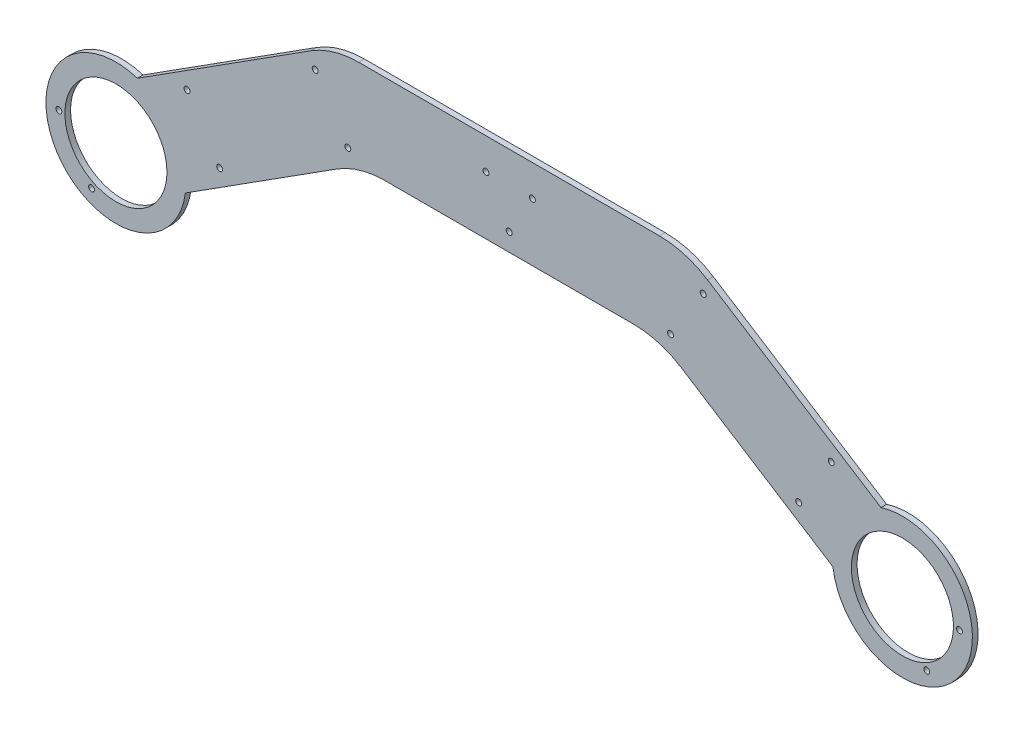
SolidWorks part; units mm, degrees
ref_plane "Front Plane" through (0, 0, 0) normal (0, 0, 1) x (1, 0, 0)
ref_plane "Top Plane" through (0, 0, 0) normal (0, 1, 0) x (1, 0, 0)
ref_plane "Right Plane" through (0, 0, 0) normal (1, 0, 0) x (0, 0, -1)
sketch "Sketch1" plane through (0, 0, 0) normal (0, 0, 1) x (1, 0, 0)
  line L0 (0, -33.2132) -> (0, -83.2132) construction
  line L1 (84.0896, -33.2132) -> (-84.0896, -33.2132)
  line L2 (-110.9546, -41.0436) -> (-262.9512, -137.8762)
  line L3 (-262.9512, -137.8762) -> (-236.0862, -180.0457)
  line L4 (-236.0862, -180.0457) -> (-96.3809, -91.0436)
  line L5 (-69.5159, -83.2132) -> (69.5159, -83.2132)
  line L6 (96.3809, -91.0436) -> (236.0862, -180.0457)
  line L7 (236.0862, -180.0457) -> (262.9512, -137.8762)
  line L8 (262.9512, -137.8762) -> (110.9546, -41.0436)
  line L9 (-98.6633, -33.2132) -> (0, 29.6422) construction
  line L10 (0, 29.6422) -> (98.6633, -33.2132) construction
  line L11 (-249.5187, -158.9609) -> (-220, -140.1555) construction
  line L12 (249.5187, -158.9609) -> (220, -140.1555) construction
  line L13 (-330, -140.1555) -> (-110, -140.1555) construction
  line L14 (-110, -140.1555) -> (110, -140.1555) construction
  line L15 (0, 0) -> (17.6777, -17.6777) construction
  line L16 (28.2843, -7.0711) -> (7.0711, -28.2843) construction
  line L17 (-7.0711, -28.2843) -> (-17.6777, -17.6777) construction
  line L18 (-17.6777, -17.6777) -> (17.6777, 17.6777) construction
  line L19 (17.6777, 17.6777) -> (28.2843, 7.0711) construction
  line L20 (17.6777, 17.6777) -> (67.5526, 17.6777) construction
  line L21 (0, -35.3553) -> (35.3553, 0) construction
  line L22 (0, 0) -> (5.7126, -24.3386) construction
  line L23 (-8.8906, -27.7661) -> (20.3157, -20.911) construction
  circle A1 centre (0, 0) radius 7.9375 construction
  circle A2 centre (-220, -140.1555) radius 110 construction
  circle A3 centre (220, -140.1555) radius 110 construction
  arc A4 (28.2843, -7.0711) -> (28.2843, 7.0711) centre (21.2132, 0) ccw construction
  arc A5 (7.0711, -28.2843) -> (-7.0711, -28.2843) centre (0, -21.2132) cw construction
  arc A6 (69.5159, -83.2132) -> (96.3809, -91.0436) centre (69.5159, -133.2132) cw
  arc A7 (-96.3809, -91.0436) -> (-69.5159, -83.2132) centre (-69.5159, -133.2132) cw
  arc A8 (110.9546, -41.0436) -> (84.0896, -33.2132) centre (84.0896, -83.2132) ccw
  arc A9 (-84.0896, -33.2132) -> (-110.9546, -41.0436) centre (-84.0896, -83.2132) ccw
  circle A10 centre (0, 0) radius 7.9375 construction
  arc A11 (20.3157, -20.911) -> (27.7661, -8.8906) centre (18.0307, -11.1756) ccw construction
  point P26 (17.6777, -17.6777)
  point P33 (35.3553, 0)
  point P36 (0, -35.3553)
  point P40 (0, -31.2132)
  dimension "D12" = 50
  dimension "D2" = 220
  dimension "D1" = 50
  dimension "D3" = 115
  dimension "D5" = 35
  dimension "D8" = 45
  dimension "D10" = 2
extrude "Base" add sketch "Sketch1" along normal blind 3.175
fillet "Fillet1" radius 10 4 edges at (262.9512, -137.8762, 1.5875) (236.0862, -180.0457, 1.5875) (-236.0862, -180.0457, 1.5875) (-262.9512, -137.8762, 1.5875)
sketch "Sketch2" plane through (0, 0, 3.175) normal (0, 0, 1) x (1, 0, 0)
  line L0 (0, -33.2132) -> (0, -83.2132) construction
  line L1 (84.0896, -33.2132) -> (-84.0896, -33.2132) construction
  line L2 (-69.5159, -83.2132) -> (69.5159, -83.2132) construction
  circle A0 centre (0, -58.2132) radius 15 construction
  circle A1 centre (-12.9904, -50.7132) radius 1.65
  circle A2 centre (12.9904, -50.7132) radius 1.65
  circle A3 centre (0, -73.2132) radius 1.65
  point P17 (0, -58.2132)
  dimension "D1" = 30
  dimension "D2" = 3.3
  dimension "D3" = 3
extrude "Adapter Attachment" cut sketch "Sketch2" against normal through all
sketch "Sketch3" plane through (0, 0, 3.175) normal (0, 0, 1) x (1, 0, 0)
  line L0 (-258.9072, -138.7727) -> (-249.1443, -140.9371) construction
  line L1 (-235.1897, -176.0018) -> (-233.0253, -166.2388) construction
  line L2 (-251.9057, -140.3249) -> (-256.2041, -133.5778) construction
  line L3 (-233.6375, -169.0002) -> (-229.3391, -175.7473) construction
  line L4 (-110.9546, -41.0436) -> (-254.5173, -132.5032) construction
  line L5 (-227.6523, -174.6727) -> (-96.3809, -91.0436) construction
  line L6 (0, -1.7463) -> (0, 1.7463) construction
  arc A0 (-254.5173, -132.5032) -> (-257.5782, -146.3101) centre (-249.1443, -140.9371) ccw construction
  arc A1 (-241.4592, -171.6118) -> (-227.6523, -174.6727) centre (-233.0253, -166.2388) ccw construction
  circle A2 centre (-251.9057, -140.3249) radius 1.65
  circle A3 centre (-233.6375, -169.0002) radius 1.65
  circle A4 centre (-161.9492, -123.3297) radius 1.65
  circle A5 centre (-180.2174, -94.6544) radius 1.65
  circle A6 centre (-90.2609, -77.6593) radius 1.65
  circle A7 centre (-108.5291, -48.984) radius 1.65
  circle A8 centre (108.5291, -48.984) radius 1.65
  circle A9 centre (90.2609, -77.6593) radius 1.65
  circle A10 centre (180.2174, -94.6544) radius 1.65
  circle A11 centre (161.9492, -123.3297) radius 1.65
  circle A12 centre (251.9057, -140.3249) radius 1.65
  circle A13 centre (233.6375, -169.0002) radius 1.65
  dimension "D2" = 3.3
  dimension "D1" = 8
  dimension "D4" = 85
  dimension "D3" = 3
extrude "Strut Holes" cut sketch "Sketch3" against normal through all
sketch "Sketch4" plane through (0, 0, 3.175) normal (0, 0, 1) x (1, 0, 0)
  line L0 (-241.9667, -135.2856) -> (-215.1301, -118.1888) construction
  line L1 (-110.9546, -41.0436) -> (-262.9512, -137.8762) construction
  line L2 (0, -1.7463) -> (0, 1.7463) construction
  circle A0 centre (-220, -140.1555) radius 16.05
  circle A1 centre (-220, -140.1555) radius 22.5 construction
  circle A2 centre (-241.9667, -135.2856) radius 2.75
  circle A3 centre (-215.1301, -118.1888) radius 2.75
  circle A4 centre (-198.0333, -145.0253) radius 2.75
  circle A5 centre (-224.8699, -162.1221) radius 2.75
  circle A6 centre (224.8699, -162.1221) radius 2.75
  circle A7 centre (241.9667, -135.2856) radius 2.75
  circle A8 centre (198.0333, -145.0253) radius 2.75
  circle A9 centre (215.1301, -118.1888) radius 2.75
  circle A10 centre (220, -140.1555) radius 16.05
  point P15 (-220, -140.1555)
  dimension "D1" = 32.1
  dimension "D2" = 45
  dimension "D4" = 5.5
  dimension "D3" = 4
extrude "Motor Connection" [suppressed] cut sketch "Sketch4" against normal through all
sketch "Sketch5" plane through (0, 0, 3.175) normal (0, 0, 1) x (1, 0, 0)
  line L0 (0, -1.7463) -> (0, 1.7463) construction
  circle A0 centre (-220, -140.1555) radius 28.55
  circle A1 centre (-220, -140.1555) radius 39.1548
  arc A2 (-254.5173, -132.5032) -> (-257.5782, -146.3101) centre (-249.1443, -140.9371) ccw construction
  circle A3 centre (-233.6375, -169.0002) radius 1.65 construction
  circle A4 centre (-251.9057, -140.3249) radius 1.65 construction
  circle A5 centre (-233.6375, -169.0002) radius 1.65
  circle A6 centre (-251.9057, -140.3249) radius 1.65
  circle A7 centre (251.9057, -140.3249) radius 1.65
  circle A8 centre (233.6375, -169.0002) radius 1.65
  circle A9 centre (220, -140.1555) radius 39.1548
  circle A10 centre (220, -140.1555) radius 28.55
  line M20 (254.5173, -132.5032) -> (110.9546, -41.0436)
  line M24 (-110.9546, -41.0436) -> (-254.5173, -132.5032)
  line M28 (-227.6523, -174.6727) -> (-96.3809, -91.0436)
  line M32 (96.3809, -91.0436) -> (227.6523, -174.6727)
  dimension "D1" = 57.1
extrude "Motor Ring" add sketch "Sketch5" against normal up to surface (3.175 mm away) up to face at (-250.2557, -140.3249, 0)
extrude "Motor Slot" cut sketch "Sketch5<2>" against normal through all contours A0 M24 M28 | A10 M32 M20 region at (-220, -140.1555, 3.175) region at (220, -140.1555, 3.175)
sketch "Sketch5<2>" plane through (0, 0, 3.175) normal (0, 0, 1) x (1, 0, 0) same geometry as "Sketch5"
equation "\"D2@Sketch1\"=\"Wheel Diameter@Rocker Bogie Assy.Assembly\""
equation "\"D1@Base\"=\"Plate Thickness@Rocker Bogie Assy.Assembly\""
